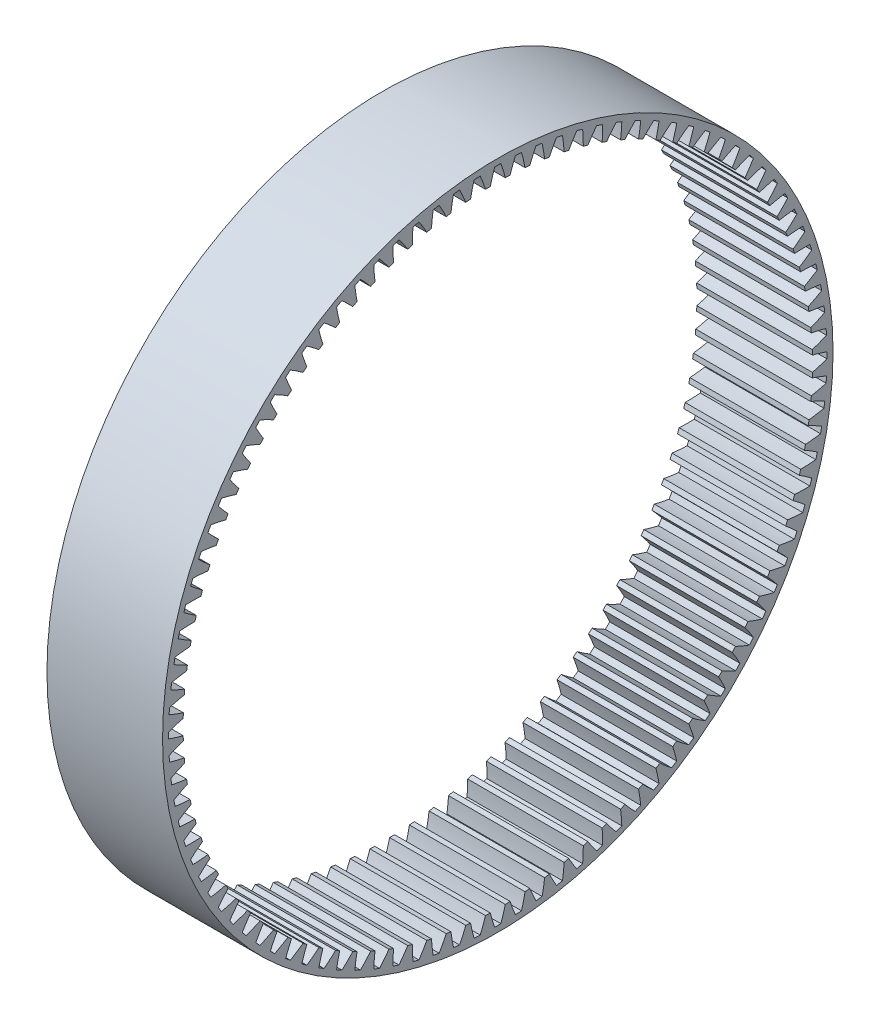
SolidWorks part; units mm, degrees
ref_plane "Plane1" through (0, 0, 0) normal (0, 0, 1) x (1, 0, 0)
ref_plane "Plane2" through (0, 0, 0) normal (0, 1, 0) x (1, 0, 0)
ref_plane "Plane3" through (0, 0, 0) normal (1, 0, 0) x (0, 0, -1)
sketch "HoldingSke" plane through (0, 0, 0) normal (0, 1, 0) x (1, 0, 0)
  line L0 (0, 0) -> (-52.928, -300.1694)
  line L1 (-15, 0) -> (100, 0) construction
  line L2 (0, 0) -> (-2.1039, 2.3779)
  line L3 (0, 0) -> (-11.863, 4.5341)
  line L4 (0, 0) -> (-1.4996, 8.5048)
  line L5 (0, 0) -> (-23.7986, -8.8762)
  line L6 (0, 0) -> (-10.5278, -7.1032)
  line L7 (-2.1039, 2.3779) -> (3.3635, 27.1825)
  line L8 (-76.2, 54.61) -> (-54.61, 54.61)
  line L9 (-67.7845, 28.3722) -> (-49.3413, 33.142)
  line L10 (-76.2, 71.12) -> (104.1128, 71.12)
  line L11 (0, 0) -> (-38.1, 0)
  line L12 (-76.2, 101.6) -> (-76.1147, 101.6)
  line L13 (24.9733, 27.94) -> (52.9518, 28.4284)
  line L14 (24.9733, 27.94) -> (24.9746, 27.94)
  line L15 (24.9733, 27.94) -> (100.4006, 29.5858)
  circle A0 centre (0, 0) radius 110.49
  circle A1 centre (0, 0) radius 12.7
  circle A2 centre (0, 0) radius 12.7
  dimension "Num_teeth" = 100
  dimension "Pitch_radius" = 180.3128
  dimension "Width" = 38.1
  dimension "Diameter" = 220.98
sketch "BasProSke" plane through (0, 0, 0) normal (0, 1, 0) x (1, 0, 0)
  line L0 (-10, 0) -> (60, 0) construction
  line L1 (0, 103.7167) -> (0, 110.49)
  line L2 (0, 103.7167) -> (38.1, 103.7167)
  line L3 (38.1, 103.7167) -> (38.1, 110.49)
  line L4 (38.1, 110.49) -> (0, 110.49)
  dimension "Thickness" = 38.1
  dimension "Diameter" = 220.98
revolve "Base-Revolve" add sketch "BasProSke" angle 360 about L0
sketch "TooCutSke" plane through (0, 0, 0) normal (1, 0, 0) x (0, 0, -1)
  line L3 (1.8757, 105.8167) -> (1.8757, 53.6633) construction
  line L4 (0, 0) -> (0, 59.563) construction
  line L5 (0, 0) -> (-2.1462, 68.2938) construction
  line L6 (-48.8437, 90.7266) -> (34.9276, 93.3592) construction
  circle A0 centre (0, 0) radius 105.8333 construction
  circle A1 centre (0, 0) radius 108.4804 construction
  circle A2 centre (0, 0) radius 92.2161 construction
  circle A3 centre (0, 0) radius 103.6913 construction
  arc A4 (2.4676, 103.6619) -> (1.0075, 108.4758) centre (-48.8437, 90.7266) ccw
  arc A5 (2.4676, 103.6619) -> (-2.4676, 103.6619) centre (0, 0) ccw
  arc A6 (1.0075, 108.4758) -> (-1.0075, 108.4758) centre (0, 0) ccw
  arc A7 (-1.0075, 108.4758) -> (-2.4676, 103.6619) centre (48.8437, 90.7266) ccw
extrude "ToothCut" cut sketch "TooCutSke" along normal through all
fillet "Breaks" [suppressed] radius 0.2117
fillet "RootFillets" [suppressed] radius 0.5304
pattern_circular "TeethCuts" count 100 every 3.6 about axis through (-10, 0, 0) along (1, 0, 0) of "RootFillets", "Breaks", "ToothCut"
equation "' \"Pitch@HoldingSke\" = 4"
equation "' \"Num_teeth@HoldingSke\" = 24"
equation "' \"Ap@HoldingSke\" =  14.5"
equation "' \"Ap@HoldingSke\" = 14.5"
equation "' \"Width@HoldingSke\" = 0.5"
equation "' \"Diameter@HoldingSke\" = 8"
equation "' \"Show_teeth@HoldingSke\" = 100"
equation "' \"Backlash@HoldingSke\" = 0.009"
equation "' \"Addendum_fac@HoldingSke\" = 1.0"
equation "' \"Dedendum_fac@HoldingSke\" = 1.25"
equation "' \"Dedendum_add@HoldingSke\" = 0.00005"
equation "' \"Clearance_fac@HoldingSke\" = 0.25"
equation "\"Overcut_dia@TooCutSke\" = (\"Num_teeth@HoldingSke\" - 2 * \"Addendum_fac@HoldingSke\") / \"Pitch@HoldingSke\" - 0.002"
equation "\"Pitch_dia@TooCutSke\" = \"Num_teeth@HoldingSke\" / \"Pitch@HoldingSke\""
equation "\"Base_dia@TooCutSke\" = \"Num_teeth@HoldingSke\" / \"Pitch@HoldingSke\" * cos((\"Ap@HoldingSke\"  * 3.14159265 / 180)) * 0.90"
equation "\"Root_dia@TooCutSke\" = \"Num_teeth@HoldingSke\"  / \"Pitch@HoldingSke\" + 2 *  \"Dedendum_fac@HoldingSke\"/ \"Pitch@HoldingSke\" + \"Dedendum_add@HoldingSke\" * 2"
equation "\"Half_ang@TooCutSke\" = 180 / \"Num_teeth@HoldingSke\""
equation "\"Half_CT@TooCutSke\" = \"Num_teeth@HoldingSke\" / \"Pitch@HoldingSke\" * sin((3.14159265 / 2 / \"Num_teeth@HoldingSke\")) / 2 + 10 * \"Backlash@HoldingSke\" / 4"
equation "\"Flank_rad@TooCutSke\" = \"Num_teeth@HoldingSke\" / \"Pitch@HoldingSke\" / 4"
equation "\"Radius@RootFillets\"= \"Clearance_fac@HoldingSke\" / \"Pitch@HoldingSke\" + \"Dedendum_add@HoldingSke\""
equation "\"Break_rad@Breaks\" = 0.02 / \"Pitch@HoldingSke\" * 5"
equation "\"Num_teeth@TeethCuts\" = int( \"Show_teeth@HoldingSke\" ) + 1"
equation "\"Num_teeth@TeethCuts\" = ((sgn( \"Num_teeth@TeethCuts\" - \"Num_teeth@HoldingSke\" )-1)*( \"Num_teeth@TeethCuts\" - \"Num_teeth@HoldingSke\" ))/-2+ \"Num_teeth@HoldingSke\""
equation "\"Num_teeth@TeethCuts\" = ((sgn( \"Num_teeth@TeethCuts\" - 2.0)+1)*( \"Num_teeth@TeethCuts\" - 2.0))/2 +2.0"
equation "\"Angle@TeethCuts\" = 360.0 / \"Num_teeth@HoldingSke\""
equation "\"Diameter@BasProSke\" = \"Num_teeth@HoldingSke\"  / \"Pitch@HoldingSke\" + 2 *  \"Dedendum_fac@HoldingSke\"/ \"Pitch@HoldingSke\" + \"Dedendum_add@HoldingSke\" * 2 + 0.002"
equation "\"Diameter@BasProSke\" = ((sgn( \"Diameter@BasProSke\"  - \"Diameter@HoldingSke\" )+1)*( \"Diameter@BasProSke\"  - \"Diameter@HoldingSke\" ))/2 + \"Diameter@HoldingSke\""
equation "\"Inside_diameter@BasProSke\" =  (\"Num_teeth@HoldingSke\" - 2 * \"Addendum_fac@HoldingSke\") / \"Pitch@HoldingSke\" "
equation "\"Thickness@BasProSke\"  = \"Width@HoldingSke\""
